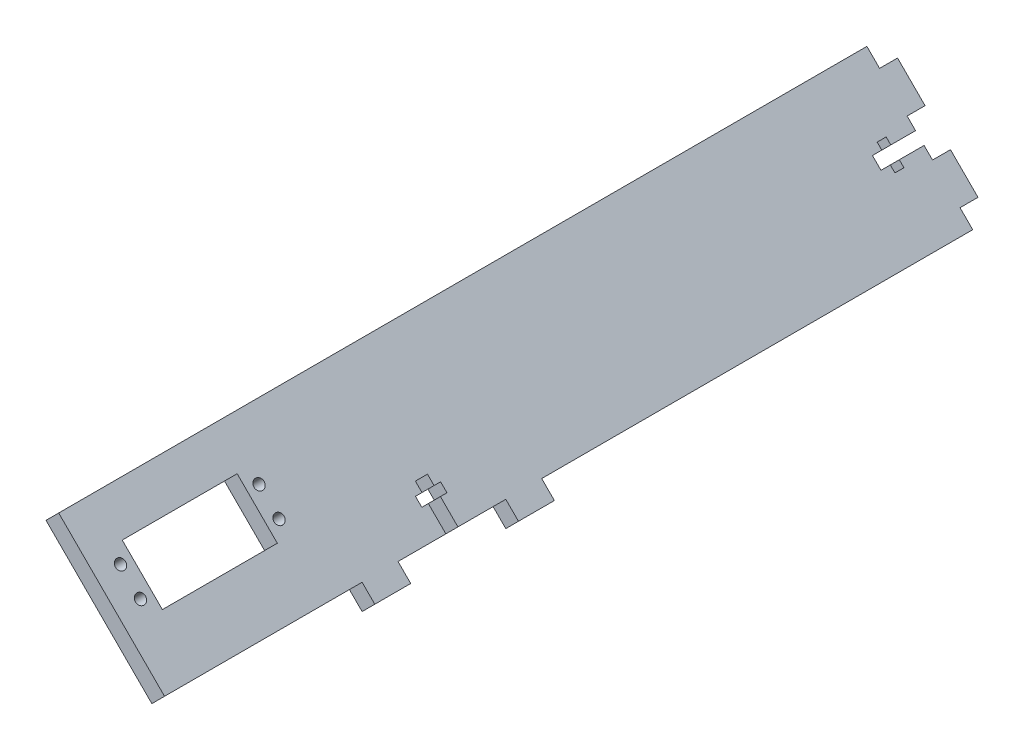
SolidWorks part; units mm, degrees
ref_plane "Front Plane" through (0, 0, 0) normal (0, 0, 1) x (1, 0, 0)
ref_plane "Top Plane" through (0, 0, 0) normal (0, 1, 0) x (1, 0, 0)
ref_plane "Right Plane" through (0, 0, 0) normal (1, 0, 0) x (0, 0, -1)
sketch "Sketch2" plane through (0, 0, 0) normal (0, 0, 1) x (1, 0, 0)
  line L0 (-71.1005, -13.7123) -> (-75.5906, -18.2024)
  line L1 (-71.1005, -13.7123) -> (-42.6562, -42.1565)
  line L2 (-75.5906, -18.2024) -> (-47.1463, -46.6467)
  line L3 (-42.6562, -42.1565) -> (-47.1463, -46.6467)
  line L4 (-75.5906, -18.2024) -> (-65.8586, -27.9344) construction
  line L5 (-61.3685, -23.4443) -> (-71.1005, -13.7123) construction
  line L6 (-47.1463, -46.6467) -> (-42.6562, -42.1565) construction
  line L7 (-71.1005, -13.7123) -> (-75.5906, -18.2024) construction
extrude "Base Extrusion" add sketch "Sketch2" along normal blind 285.75
sketch "Sketch3" plane through (-46.8965, -46.8965, 0) normal (-0.7071, -0.7071, 0) x (0, 0, 1)
  line L0 (0, 20.4664) -> (24.1393, 20.4664) construction
  line L1 (0, 40.5796) -> (0, 0.3533) construction
  line B0 (0, 22.6) -> (0, 18.3328)
  line B1 (11.938, 18.3328) -> (11.938, 16.0214)
  line B2 (11.938, 16.0214) -> (8.763, 16.0214)
  line B3 (8.763, 16.0214) -> (8.763, 18.3328)
  line B4 (8.763, 18.3328) -> (0, 18.3328)
  line B5 (11.938, 18.3328) -> (15.24, 18.3328)
  line B6 (15.24, 18.3328) -> (15.24, 22.6)
  line B7 (11.938, 22.6) -> (15.24, 22.6)
  line B8 (8.763, 22.6) -> (0, 22.6)
  line B9 (8.763, 24.9114) -> (8.763, 22.6)
  line B10 (11.938, 24.9114) -> (8.763, 24.9114)
  line B11 (11.938, 22.6) -> (11.938, 24.9114)
sketch_block_instance "TSlot-1"
sketch_block "TSlot" parameters "D1"=3.302, "D2"=3.175
extrude "Base T Slot" cut sketch "Sketch3" against normal through all
sketch "Sketch4" plane through (0, 0, 0) normal (0, 0, -1) x (-1, 0, 0)
  line L0 (75.5906, -18.2024) -> (65.8586, -27.9344) construction
  line L1 (65.8586, -27.9344) -> (61.3685, -23.4443) construction
  line L2 (61.3685, -23.4443) -> (71.1005, -13.7123) construction
  line L3 (71.1005, -13.7123) -> (75.5906, -18.2024) construction
  line L4 (42.6562, -42.1565) -> (52.3882, -32.4245) construction
  line L5 (52.3882, -32.4245) -> (56.8783, -36.9147) construction
  line L6 (56.8783, -36.9147) -> (47.1463, -46.6467) construction
  line L7 (47.1463, -46.6467) -> (42.6562, -42.1565) construction
  line L8 (75.5906, -18.2024) -> (65.8586, -27.9344)
  line L9 (65.8586, -27.9344) -> (61.3685, -23.4443)
  line L10 (61.3685, -23.4443) -> (71.1005, -13.7123)
  line L11 (71.1005, -13.7123) -> (75.5906, -18.2024)
  line L12 (42.6562, -42.1565) -> (52.3882, -32.4245)
  line L13 (52.3882, -32.4245) -> (56.8783, -36.9147)
  line L14 (56.8783, -36.9147) -> (47.1463, -46.6467)
  line L15 (47.1463, -46.6467) -> (42.6562, -42.1565)
extrude "Base Tabs" add sketch "Sketch4" along normal blind 6.35
sketch "Sketch5" plane through (-42.4064, -42.4064, 0) normal (0.7071, 0.7071, 0) x (0, 0, -1)
  line L1 (-273.05, 33.1193) -> (-232.41, 33.1193)
  line L2 (-273.05, 33.1193) -> (-273.05, 13.0533)
  line L3 (-273.05, 13.0533) -> (-232.41, 13.0533)
  line L4 (-232.41, 33.1193) -> (-232.41, 13.0533)
  line L5 (-285.75, 0.3533) -> (-285.75, 40.5796) construction
  line L6 (-264.2152, 33.1193) -> (-238.1965, 33.1193) construction
  line L7 (-238.1965, 13.0533) -> (-263.3345, 13.0533) construction
  line L8 (-264.2152, 33.1193) -> (-238.1965, 33.1193) construction
  line L9 (-238.1965, 13.0533) -> (-263.3345, 13.0533) construction
  dimension "D1" = 40.64
  dimension "D2" = 12.7
extrude "Servo Slot" cut sketch "Sketch5" against normal through all
sketch "Sketch6" plane through (-42.4064, -42.4064, 0) normal (0.7071, 0.7071, 0) x (0, 0, -1)
  arc A4 (-278.4743, 26.8163) -> (-278.4743, 29.3563) centre (-277.23, 28.0863) ccw construction
  arc A5 (-278.4743, 16.8163) -> (-278.4743, 19.3563) centre (-277.23, 18.0863) ccw construction
  arc A6 (-226.9857, 29.3563) -> (-226.9857, 26.8163) centre (-228.23, 28.0863) ccw construction
  arc A7 (-226.9857, 19.3563) -> (-226.9857, 16.8163) centre (-228.23, 18.0863) ccw construction
  circle A8 centre (-277.23, 28.0863) radius 1.778
  circle A9 centre (-277.23, 18.0863) radius 1.778
  circle A10 centre (-228.23, 28.0863) radius 1.778
  circle A11 centre (-228.23, 18.0863) radius 1.778
extrude "Servo Mounting Holes" cut sketch "Sketch6" against normal through all
sketch "Sketch7" plane through (0, 0, 285.75) normal (0, 0, 1) x (1, 0, 0)
  line L0 (-47.1463, -46.6467) -> (-42.6562, -42.1565)
  line L1 (-47.1463, -46.6467) -> (-42.6562, -51.1368)
  line L2 (-42.6562, -42.1565) -> (-38.1661, -46.6467)
  line L3 (-42.6562, -51.1368) -> (-38.1661, -46.6467)
  line L4 (-74.9484, -83.429) -> (-72.2727, -80.7533) construction
  line L5 (-75.5906, -18.2024) -> (-71.1005, -13.7123)
  line L6 (-75.5906, -18.2024) -> (-80.0807, -13.7123)
  line L7 (-71.1005, -13.7123) -> (-75.5906, -9.2222)
  line L8 (-80.0807, -13.7123) -> (-75.5906, -9.2222)
extrude "Filler Extrusion to Funnel Support" add sketch "Sketch7" against normal up to surface (285.75 mm away)
sketch "Sketch8" plane through (-42.4064, -42.4064, 0) normal (0.7071, 0.7071, 0) x (0.7071, -0.7071, 0)
  line L0 (28.1183, -184.15) -> (-82.975, -184.15) construction
  line L1 (-13.8727, -82.55) -> (3.0437, -82.55) construction
  line L2 (5.9967, -285.75) -> (-46.9296, -285.75) construction
  line L3 (5.9967, -285.75) -> (5.9967, -215.9) construction
  line B0 (5.9967, -186.2836) -> (5.9967, -182.0164)
  line B1 (-5.9413, -182.0164) -> (-5.9413, -179.705)
  line B2 (-5.9413, -179.705) -> (-2.7663, -179.705)
  line B3 (-2.7663, -179.705) -> (-2.7663, -182.0164)
  line B4 (-2.7663, -182.0164) -> (5.9967, -182.0164)
  line B5 (-5.9413, -182.0164) -> (-9.2433, -182.0164)
  line B6 (-9.2433, -182.0164) -> (-9.2433, -186.2836)
  line B7 (-5.9413, -186.2836) -> (-9.2433, -186.2836)
  line B8 (-2.7663, -186.2836) -> (5.9967, -186.2836)
  line B9 (-2.7663, -188.595) -> (-2.7663, -186.2836)
  line B10 (-5.9413, -188.595) -> (-2.7663, -188.595)
  line B11 (-5.9413, -186.2836) -> (-5.9413, -188.595)
sketch_block_instance "TSlot-2"
extrude "Side T Slot" cut sketch "Sketch8" against normal through all
sketch "Sketch9" plane through (4.2403, -4.2403, 0) normal (0.7071, -0.7071, 0) x (-0.7071, -0.7071, 0)
  line L0 (49.5253, -247.9715) -> (49.5253, -199.7444) construction
  line L1 (66.3217, -186.2836) -> (66.3217, -285.75) construction
  line L2 (66.3217, -215.9) -> (59.9717, -215.9)
  line L3 (66.3217, -215.9) -> (66.3217, -203.2)
  line L4 (66.3217, -203.2) -> (59.9717, -203.2)
  line L5 (59.9717, -215.9) -> (59.9717, -203.2)
  line L6 (59.9717, -186.2836) -> (59.9717, -285.75) construction
  line L7 (66.3217, 0) -> (66.3217, -182.0164) construction
  line L8 (66.3217, -165.1) -> (59.9717, -165.1)
  line L9 (66.3217, -165.1) -> (66.3217, -152.4)
  line L10 (66.3217, -152.4) -> (59.9717, -152.4)
  line L11 (59.9717, -165.1) -> (59.9717, -152.4)
  line L12 (59.9717, 0) -> (59.9717, -182.0164) construction
  line L13 (104.7498, -184.15) -> (30.8469, -184.15) construction
  line L14 (66.3217, -285.75) -> (59.9717, -285.75) construction
  line L15 (41.5779, -82.55) -> (59.9717, -82.55) construction
  dimension "D1" = 12.7
  dimension "D2" = 19.05
extrude "Side Tabs" add sketch "Sketch9" along normal up to surface (6.35 mm away)
